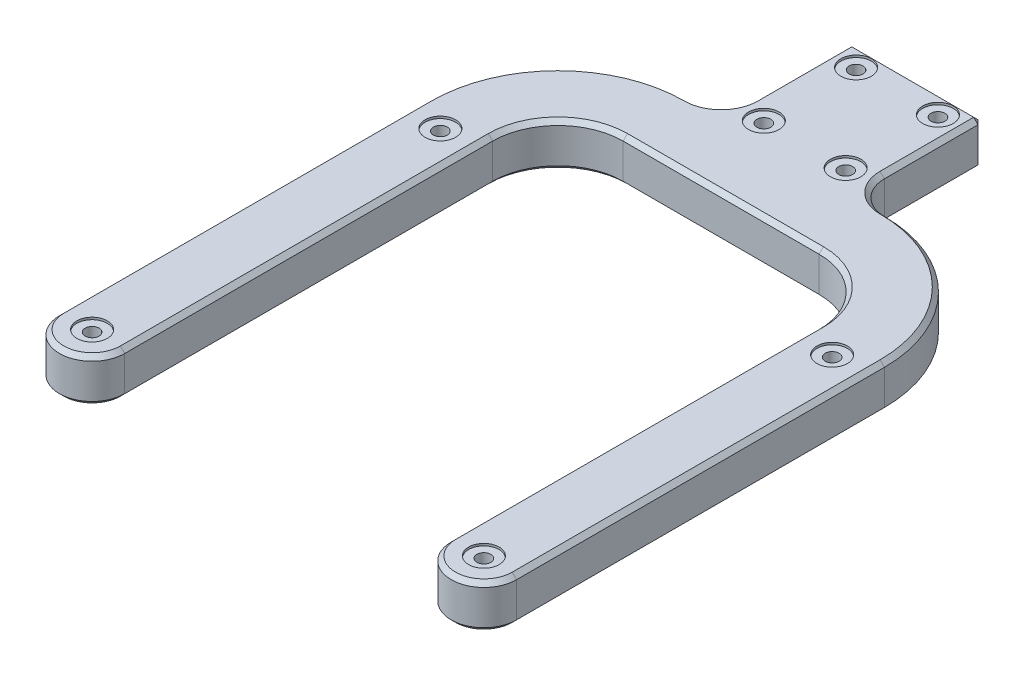
SolidWorks part; units mm, degrees
material "ABS PC"
ref_plane "Front Plane" through (0, 0, 0) normal (0, 0, 1) x (1, 0, 0)
ref_plane "Top Plane" through (0, 0, 0) normal (0, 1, 0) x (1, 0, 0)
ref_plane "Right Plane" through (0, 0, 0) normal (1, 0, 0) x (0, 0, -1)
sketch "Sketch1" plane through (0, 0, 0) normal (0, 1, 0) x (1, 0, 0)
  line L0 (22.5, 57.25) -> (0, 57.25)
  line L1 (0, 57.25) -> (0, 102.25)
  line L2 (37.5, 42.25) -> (37.5, -42.25)
  line L7 (15, 102.25) -> (0, 102.25)
  line L8 (0, 0) -> (0, 57.25) construction
  line L9 (15, 102.25) -> (15, 72.25)
  line L13 (15, 72.25) -> (22.5, 72.25)
  line L14 (52.5, 42.25) -> (52.5, -42.25)
  arc A4 (22.5, 57.25) -> (37.5, 42.25) centre (22.5, 42.25) cw
  arc A6 (22.5, 72.25) -> (52.5, 42.25) centre (22.5, 42.25) cw
  circle A7 centre (9.4, 97.65) radius 1.6
  circle A8 centre (9.4, 76.45) radius 1.6
  arc A9 (37.5, -42.25) -> (52.5, -42.25) centre (45, -42.25) ccw
  circle A10 centre (45, 37.75) radius 1.6
  circle A11 centre (45, -42.25) radius 1.6
  point P10 (37.5, 0)
  point P24 (0, 0)
  point P25 (45, -42.25)
  point P26 (0, 0)
  dimension "D7" = 80
  dimension "D8" = 30
  dimension "D9" = 15
  dimension "D10" = 3.2
  dimension "D11" = 18
  dimension "D12" = 3
  dimension "D13" = 4
  dimension "D6" = 107
  dimension "D14" = 3.2
  dimension "D1" = 15
  dimension "D2" = 15
  dimension "D3" = 30
  dimension "D4" = 30
  dimension "D5" = 75
extrude "Boss-Extrude1" add sketch "Sketch1" along normal blind 10
sketch "Sketch4" plane through (0, 10, 0) normal (0, 1, 0) x (1, 0, 0)
  circle A0 centre (9.4, 97.65) radius 3.5
  circle A1 centre (9.4, 76.45) radius 3.5
  circle A2 centre (45, 37.75) radius 3.5
  circle A3 centre (45, -42.25) radius 3.5
  dimension "D1" = 7
extrude "Cut-Extrude1" cut sketch "Sketch4" against normal blind 0.5
fillet "Fillet1" radius 7.5 1 edges at (15, 5, -72.25)
chamfer "Chamfer1" distance 1 angle 45 19 edges at (11.25, 0, -57.25) (33.1066, 0, -52.8566) (37.5, 0, 0) (52.5, 0, 0) (43.7132, 0, -63.4632) (15, 0, -91) (7.5, 0, -102.25) (11.25, 10, -57.25) (33.1066, 10, -52.8566) (37.5, 10, 0) (52.5, 10, 0) (43.7132, 10, -63.4632) (15, 10, -91) (7.5, 10, -102.25) (17.1967, 0, -74.4467) (17.1967, 10, -74.4467) (15, 5, -102.25) (45, 0, 49.75) (45, 10, 49.75)
mirror "Mirror1" about plane through (0, 10, -57.25) normal (1, 0, 0) of bodies 103 101
